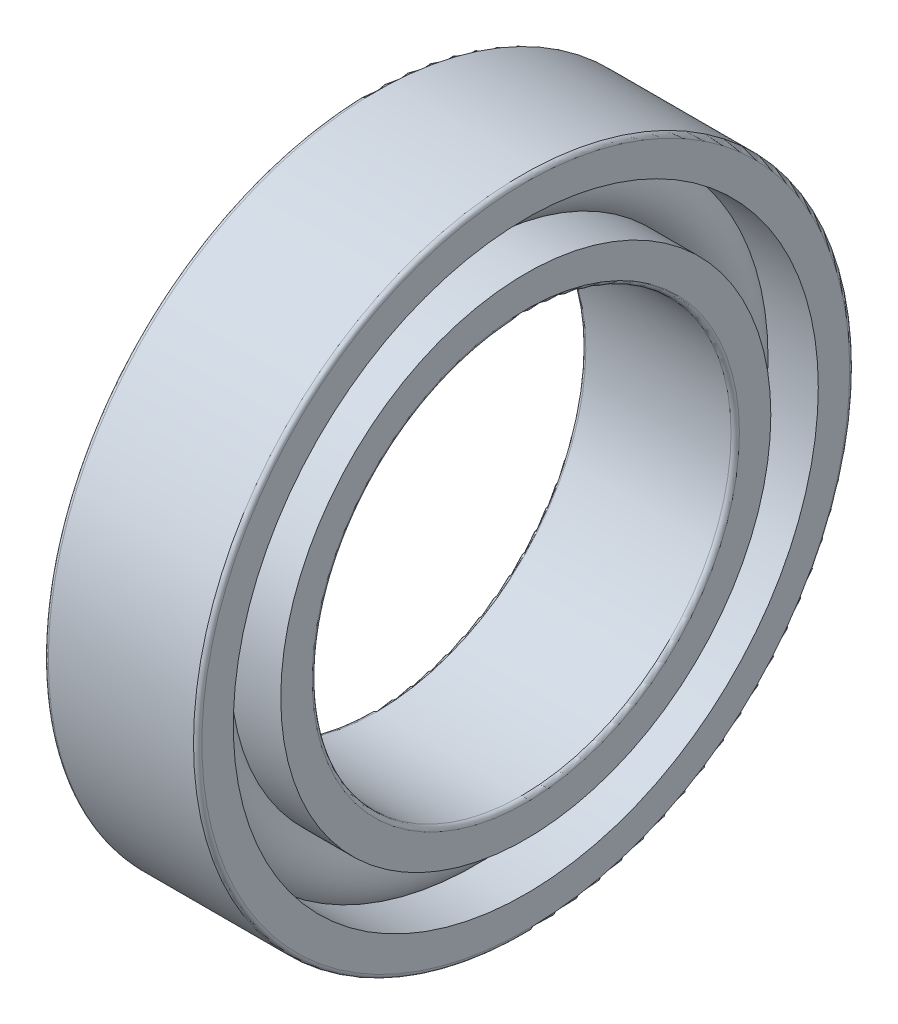
SolidWorks part; units mm, degrees
material "1023 Carbon Steel Sheet (SS)"
ref_plane "Plane1" through (0, 0, 0) normal (0, 0, 1) x (1, 0, 0)
ref_plane "Plane2" through (0, 0, 0) normal (0, 1, 0) x (1, 0, 0)
ref_plane "Plane3" through (0, 0, 0) normal (1, 0, 0) x (0, 0, -1)
other "Configuration Table"
sketch "Clipboard" plane through (0, 0, 0) normal (0, 0, 1) x (1, 0, 0)
  line L0 (-10, 0) -> (10, 0) construction
  line L1 (0, 0) -> (22.3471, -0.7804)
  line L2 (0, 0) -> (19.2383, 0.6718)
  line L3 (0, 0) -> (22.3471, -0.7804)
  line L4 (0, 0) -> (-22.3573, -0.3902)
  dimension "BallCLRad" = 19.25
sketch "CagSpiSke" plane through (0, 0, 0) normal (0, 0, 1) x (1, 0, 0)
  line L0 (0.255, 18.825) -> (0.255, 19.675)
  line L1 (0.255, 19.675) -> (-0.255, 19.675)
  line L2 (-0.255, 19.675) -> (-0.255, 18.825)
  line L3 (-0.255, 18.825) -> (0.255, 18.825)
  line L4 (-20.6375, 0) -> (20.6375, 0) construction
  line L5 (0, 0) -> (0, 23.7692) construction
  dimension "OD" = 39.35
  dimension "ID" = 37.65
revolve "CageSpine" add sketch "CagSpiSke" angle 0.001 about L4 reverse direction yes
ref_axis "Axis1" through (-50, 0, 0) along (1, 0, 0)
sketch "CagBalSke" plane through (0, 0, 0) normal (0, 0, 1) x (1, 0, 0)
  line L0 (-2.805, 19.25) -> (2.805, 19.25)
  line L1 (-1.905, 19.25) -> (1.905, 19.25) construction
  line L2 (-10, 0) -> (10, 0) construction
  line L3 (0, 0) -> (0, 24) construction
  arc A0 (2.805, 19.25) -> (-2.805, 19.25) centre (0, 19.25) cw
  dimension "BallCLRad" = 19.25
revolve "CageBall" [suppressed] add sketch "CagBalSke" angle 360 about L1 reverse direction yes
pattern_circular "CageBalls" [suppressed] count 2 every 180 about axis through (-50, 0, 0) along (1, 0, 0)
sketch "CagTrmODSke" plane through (0, 0, 0) normal (0, 0, 1) x (1, 0, 0)
  line L0 (2.806, 19.675) -> (2.806, 22.056)
  line L1 (2.806, 22.056) -> (-2.806, 22.056)
  line L2 (-2.806, 22.056) -> (-2.806, 19.675)
  line L3 (-2.806, 19.675) -> (2.806, 19.675)
  line L4 (-20.6375, 0) -> (20.6375, 0) construction
  line L5 (0, 0) -> (0, 25) construction
  dimension "Width" = 5.612
  dimension "ID" = 39.35
  dimension "OD" = 44.112
revolve "CageTrimOD" [suppressed] cut sketch "CagTrmODSke" angle 360 about L4 reverse direction yes
sketch "CagTrmIDSke" plane through (0, 0, 0) normal (0, 0, 1) x (1, 0, 0)
  line L0 (2.806, 16.446) -> (2.806, 18.825)
  line L1 (2.806, 18.825) -> (-2.806, 18.825)
  line L2 (-2.806, 18.825) -> (-2.806, 16.446)
  line L3 (-2.806, 16.446) -> (2.806, 16.446)
  line L4 (-20.6375, 0) -> (20.6375, 0) construction
  line L5 (0, 0) -> (0, 25) construction
  dimension "Width" = 5.612
  dimension "ID" = 32.892
  dimension "OD" = 37.65
revolve "CageTrimID" [suppressed] cut sketch "CagTrmIDSke" angle 360 about L4 reverse direction yes
sketch "BalSimSke" plane through (0, 0, 0) normal (0, 0, 1) x (1, 0, 0)
  line L0 (-10, 0) -> (10, 0) construction
  line L1 (-10, 19.25) -> (10, 19.25) construction
  line L2 (0, 0) -> (0, 23) construction
  circle A0 centre (0, 19.25) radius 2.55
  dimension "BallCLRad" = 19.25
  dimension "Ball_diameter" = 5.1
revolve "BallsSimplified" add sketch "BalSimSke" angle 360 about L0
sketch "BalDetSke" plane through (0, 0, 0) normal (0, 0, 1) x (1, 0, 0)
  line L0 (-2.55, 19.25) -> (2.55, 19.25)
  line L1 (-1.905, 19.25) -> (1.905, 19.25) construction
  line L2 (0, 0) -> (0, 25) construction
  arc A0 (2.55, 19.25) -> (-2.55, 19.25) centre (0, 19.25) cw
  dimension "BallCLRad" = 19.25
  dimension "Ball_diameter" = 5.1
revolve "BallDetailed" [suppressed] add sketch "BalDetSke" angle 360 about L1 reverse direction yes
sketch "InnRacSke" plane through (0, 0, 0) normal (0, 0, 1) x (1, 0, 0)
  line L0 (-1.867, 17.55) -> (-5.5, 17.55)
  line L1 (-5.5, 17.55) -> (-5.5, 15.3)
  line L2 (-5.2, 15) -> (5.2, 15)
  line L3 (5.5, 15.3) -> (5.5, 17.55)
  line L4 (5.5, 17.55) -> (1.867, 17.55)
  line L5 (-20.6375, 0) -> (20.6375, 0) construction
  line L6 (0, 0) -> (0, 30) construction
  arc A0 (-5.5, 15.3) -> (-5.2, 15) centre (-5.2, 15.3) ccw
  arc A1 (5.2, 15) -> (5.5, 15.3) centre (5.2, 15.3) ccw
  arc A2 (1.867, 17.55) -> (-1.867, 17.55) centre (0, 19.25) cw
  dimension "BallCLRad" = 19.25
  dimension "Fillet_radius" = 0.3
  dimension "Ball_diameter" = 5.05
  dimension "ID" = 30
  dimension "OD" = 35.1
  dimension "Width" = 11
revolve "InnerRace" add sketch "InnRacSke" angle 360 about L5 reverse direction yes
sketch "OutRacSke" plane through (0, 0, 0) normal (0, 0, 1) x (1, 0, 0)
  line L0 (-1.867, 20.95) -> (-5.5, 20.95)
  line L1 (-5.5, 20.95) -> (-5.5, 23.2)
  line L2 (-5.2, 23.5) -> (5.2, 23.5)
  line L3 (5.5, 23.2) -> (5.5, 20.95)
  line L4 (5.5, 20.95) -> (1.867, 20.95)
  line L5 (-20.6375, 0) -> (20.6375, 0) construction
  line L6 (0, 0) -> (0, 30) construction
  arc A0 (-5.5, 23.2) -> (-5.2, 23.5) centre (-5.2, 23.2) cw
  arc A1 (5.2, 23.5) -> (5.5, 23.2) centre (5.2, 23.2) cw
  arc A2 (1.867, 20.95) -> (-1.867, 20.95) centre (0, 19.25) ccw
  dimension "BallCLRad" = 19.25
  dimension "Fillet_radius" = 0.3
  dimension "Ball_diameter" = 5.05
  dimension "Width" = 11
revolve "OuterRace" add sketch "OutRacSke" angle 360 about L5 reverse direction yes
pattern_circular "BallsDetailed" [suppressed] count 2 every 180 about axis through (-50, 0, 0) along (1, 0, 0)
equation "\"BallCLRad@Clipboard\" = ( \"OD@OutRacSke\" + \"ID@InnRacSke\" ) / 4"
equation "\"BallCLRad@BalSimSke\" = \"BallCLRad@Clipboard\""
equation "\"BallCLRad@BalDetSke\" = \"BallCLRad@Clipboard\""
equation "\"BallCLRad@InnRacSke\" = \"BallCLRad@Clipboard\""
equation "\"BallCLRad@OutRacSke\" = \"BallCLRad@Clipboard\""
equation "\"Ball_diameter@InnRacSke\" = \"Ball_diameter@BalDetSke\" - 0.05"
equation "\"Ball_diameter@OutRacSke\" = \"Ball_diameter@BalDetSke\" - 0.05"
equation "\"Ball_diameter@BalSimSke\" = \"Ball_diameter@BalDetSke\""
equation "\"Width@OutRacSke\" = \"Width@InnRacSke\""
equation "\"Fillet_radius@OutRacSke\" = \"Fillet_radius@InnRacSke\""
equation "\"Max_count@Clipboard\" = int( 3.14159265 / atn(( \"Ball_diameter@BalDetSke\" / 2) / sqr( \"BallCLRad@Clipboard\"  *  \"BallCLRad@Clipboard\" - ( \"Ball_diameter@BalDetSke\" / 2) *  ( \"Ball_diameter@BalDetSke\" / 2))))"
equation "\"Max_count@Clipboard\" = ((sgn( \"Max_count@Clipboard\" - \"Count@Clipboard\" )-1)*( \"Max_count@Clipboard\" - \"Count@Clipboard\" ))/-2+ \"Count@Clipboard\""
equation "\"Count@BallsDetailed\" = int( \"Show_count@Clipboard\" ) "
equation "\"Count@BallsDetailed\" = ((sgn( \"Count@BallsDetailed\" - \"Max_count@Clipboard\" )-1)*( \"Count@BallsDetailed\" - \"Max_count@Clipboard\" ))/-2+ \"Max_count@Clipboard\""
equation "\"Count@BallsDetailed\" = ((sgn( \"Count@BallsDetailed\" - \"Min_count@Clipboard\" )+1)*( \"Count@BallsDetailed\" - \"Min_count@Clipboard\"))/2 +\"Min_count@Clipboard\""
equation "\"Angle@BallsDetailed\" = 360.0 / \"Max_count@Clipboard\""
equation "\"BallCLRad@CagBalSke\" = \"BallCLRad@Clipboard\""
equation "\"Count@CageBalls\" = \"Count@BallsDetailed\""
equation "\"Angle@CageBalls\" = \"Angle@BallsDetailed\""
equation "\"Angle@CageSpine\" =  \"Angle@CageBalls\" * ( \"Count@CageBalls\" -1 + int( \"Count@CageBalls\" / \"Max_count@Clipboard\" ) )  + 0.001 -  int( \"Count@CageBalls\" / \"Max_count@Clipboard\" ) * 0.001"
equation "\"Angle@CageSpine\" =  \"Angle@CageSpine\" * int( \"Min_count@Clipboard\" / 2) + int(1 / \"Min_count@Clipboard\")  * 0.001"
equation "\"CageWallOD@CagBalSke\" =  \"Ball_diameter@BalDetSke\" * 1.1"
equation "\"Thickness@CagSpiSke\" =  \"Ball_diameter@BalDetSke\" * 0.1"
equation "\"OD@CagTrmODSke\" = \"BallCLRad@Clipboard\" * 2 + \"CageWallOD@CagBalSke\" + 0.002"
equation "\"ID@CagTrmODSke\" = \"BallCLRad@Clipboard\" * 2 + \"Ball_diameter@BalDetSke\" / 6"
equation "\"OD@CagTrmIDSke\" = \"BallCLRad@Clipboard\" * 2 - \"Ball_diameter@BalDetSke\" / 6"
equation "\"ID@CagTrmIDSke\" = \"BallCLRad@Clipboard\" * 2 - \"CageWallOD@CagBalSke\" + 0.002"
equation "\"OD@CagSpiSke\" = \"ID@CagTrmODSke\""
equation "\"ID@CagSpiSke\" = \"OD@CagTrmIDSke\""
equation "\"Width@CagTrmODSke\" = \"CageWallOD@CagBalSke\" + 0.002"
equation "\"Width@CagTrmIDSke\" = \"CageWallOD@CagBalSke\" + 0.002"
